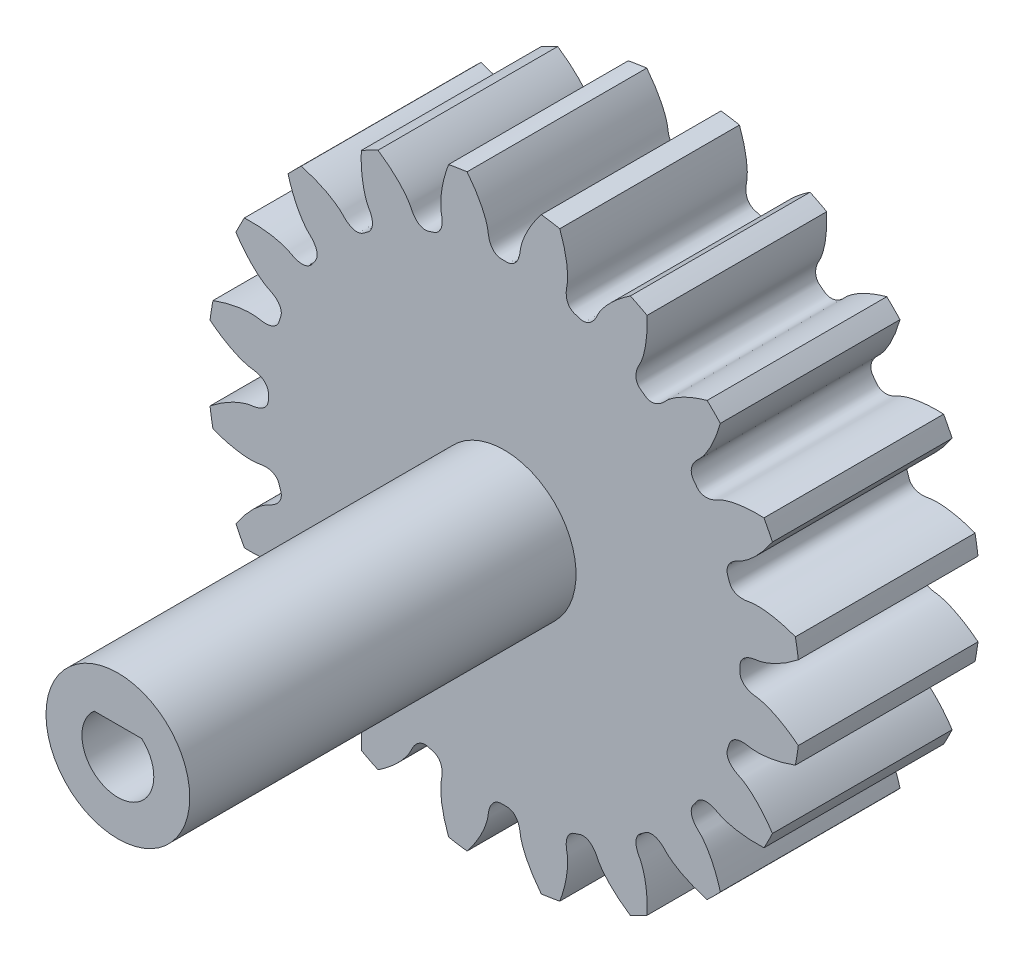
SolidWorks part; units mm, degrees
ref_plane "Front Plane" through (0, 0, 0) normal (0, 0, 1) x (1, 0, 0)
ref_plane "Top Plane" through (0, 0, 0) normal (0, 1, 0) x (1, 0, 0)
ref_plane "Right Plane" through (0, 0, 0) normal (1, 0, 0) x (0, 0, -1)
ref_axis "Axis1" through (0, 0, 55) along (0, 0, -1)
sketch "SketchRevolveSpurAssembly01Pinion" plane through (0, 0, 0) normal (1, 0, 0) x (0, 0, -1)
  line L0 (0, 0) -> (1, 0) construction
  line L1 (-5, 0) -> (-5, 16.5)
  line L2 (-5, 16.5) -> (5, 16.5)
  line L3 (5, 16.5) -> (5, 0)
  line L4 (5, 0) -> (-5, 0)
  dimension "Side1" = 5
  dimension "OutsideRadius" = 16.5
  dimension "Side2" = 5
revolve "SpurAssembly01Pinion" add sketch "SketchRevolveSpurAssembly01Pinion" angle 360 about L0
sketch "SketchToothSpurAssembly01Pinion" plane through (0, 0, 0) normal (0, 0, 1) x (1, 0, 0)
  arc A0 (16.4388, 2.1204) -> (16.4388, -2.1204) centre (0, 0) cw
  spline S0 degree 3 poles (16.4388, -2.1204) (16.3062, -2.0126) (16.1079, -1.8609) (15.8417, -1.6767) (15.6549, -1.5557) (15.4759, -1.4476) (15.3054, -1.3516) (15.1441, -1.2672) (14.9923, -1.1937) (14.8506, -1.1305) (14.7196, -1.0767) (14.5996, -1.0318) (14.491, -0.9949) (14.3942, -0.9653) (14.3096, -0.9423) (14.2375, -0.925) (14.178, -0.9126) (14.0492, -0.8903) (13.9123, -0.8782) (13.7697, -0.8427) (13.6956, -0.8206) (13.6244, -0.795) (13.5557, -0.7654) (13.4893, -0.7311) (13.4248, -0.6913) (13.3623, -0.6446) (13.3021, -0.5892) (13.2452, -0.523) (13.1943, -0.4439) (13.1533, -0.3509) (13.1303, -0.2534) (13.1208, -0.135) (13.1277, 0) (13.1208, 0.135) (13.1303, 0.2534) (13.1533, 0.3509) (13.1943, 0.4439) (13.2452, 0.523) (13.3021, 0.5892) (13.3623, 0.6446) (13.4248, 0.6913) (13.4893, 0.7311) (13.5557, 0.7654) (13.6244, 0.795) (13.6956, 0.8206) (13.7697, 0.8427) (13.9123, 0.8782) (14.0492, 0.8903) (14.178, 0.9126) (14.2375, 0.925) (14.3096, 0.9423) (14.3942, 0.9653) (14.491, 0.9949) (14.5996, 1.0318) (14.7196, 1.0767) (14.8506, 1.1305) (14.9923, 1.1937) (15.1441, 1.2672) (15.3054, 1.3516) (15.4759, 1.4476) (15.6549, 1.5557) (15.8417, 1.6767) (16.1079, 1.8609) (16.3062, 2.0126) (16.4388, 2.1204) knots 0 0 0 0 0.061423 0.08971 0.11638 0.141434 0.164872 0.186693 0.206898 0.225486 0.242459 0.257814 0.271554 0.283677 0.294183 0.303073 0.310347 0.316004 0.350077 0.359568 0.368803 0.377844 0.386769 0.395676 0.404689 0.413963 0.423683 0.434051 0.445256 0.457401 0.47042 0.481067 0.5 0.518933 0.52958 0.542599 0.554744 0.565949 0.576317 0.586037 0.595311 0.604324 0.613231 0.622156 0.631197 0.640432 0.649923 0.683996 0.689653 0.696927 0.705817 0.716323 0.728446 0.742186 0.757541 0.774514 0.793102 0.813307 0.835128 0.858566 0.88362 0.91029 0.938577 1 1 1 1
extrude "ToothExtrudeCutSpurAssembly01Pinion" cut sketch "SketchToothSpurAssembly01Pinion" against normal blind 5 and the other way blind 5
pattern_circular "PatternSpurAssembly01Pinion" count 20 over 360 about axis through (0, 0, 55) along (0, 0, -1) of "ToothExtrudeCutSpurAssembly01Pinion"
sketch "AuxiliarySketchSpurAssembly01Pinion" plane through (0, 0, 0) normal (0, 0, 1) x (1, 0, 0)
  circle A0 centre (0, 0) radius 15 construction
  circle A1 centre (0, 0) radius 14.0954 construction
  circle A2 centre (0, 0) radius 14.1048 construction
  circle A3 centre (0, 0) radius 16.5 construction
  circle A4 centre (0, 0) radius 13.125 construction
  dimension "PitchDiameter" = 30
  dimension "BaseDiameter" = 28.1908
  dimension "FormDiameter" = 28.2095
  dimension "MajorDiameter" = 33
  dimension "MinorDiameter" = 26.25
sketch "Sketch1" plane through (0, 0, 5) normal (0, 0, 1) x (1, 0, 0)
  circle A0 centre (0, 0) radius 4
extrude "Boss-Extrude1" add sketch "Sketch1" along normal blind 21.5
sketch "Sketch7" plane through (0, 0, 26.5) normal (0, 0, 1) x (1, 0, 0)
  line L0 (0, 0) -> (0, 1.5) construction
  line L1 (1.3229, 1.5) -> (-1.3229, 1.5)
  circle A0 centre (0, 0) radius 2 construction
  arc A1 (1.3229, 1.5) -> (-1.3229, 1.5) centre (0, 0) cw
  point P10 (0, 1.5)
extrude "Cut-Extrude5" cut sketch "Sketch7" against normal blind 8 contours L1 A1
sketch "Sketch8" plane through (0, 0, -5) normal (0, 0, -1) x (-1, 0, 0)
  circle A0 centre (0, 0) radius 4
extrude "Boss-Extrude5" add sketch "Sketch8" along normal blind 5
